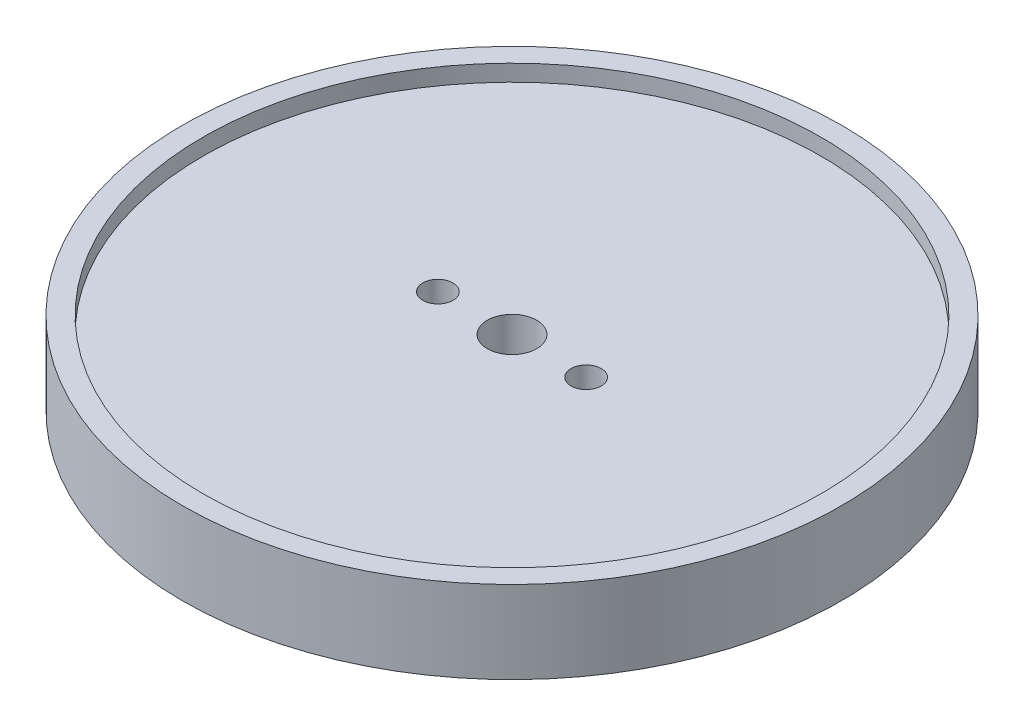
SolidWorks part; units mm, degrees
ref_plane "Front Plane" through (0, 0, 0) normal (0, 0, 1) x (1, 0, 0)
ref_plane "Top Plane" through (0, 0, 0) normal (0, 1, 0) x (1, 0, 0)
ref_plane "Right Plane" through (0, 0, 0) normal (1, 0, 0) x (0, 0, -1)
sketch "Sketch2" plane through (0, 0, 0) normal (0, 1, 0) x (1, 0, 0)
  line L0 (0, 0) -> (9, 0) construction
  line L1 (0, 0) -> (0, 20.4928) construction
  circle A0 centre (0, 0) radius 40
  circle A1 centre (0, 0) radius 3
  circle A2 centre (9, 0) radius 1.835
  circle A3 centre (-9, 0) radius 1.835
  circle A4 centre (0, 0) radius 37.5
  dimension "D1" = 80
  dimension "D2" = 6
  dimension "D4" = 3.67
  dimension "D5" = 75
  dimension "D3" = 9
extrude "Boss-Extrude1" add sketch "Sketch2" along normal blind 10 contours A0 A4 region at (-38.8686, 0, 0)
extrude "Boss-Extrude2" add sketch "Sketch2<4>" along normal blind 8 contours A4 A3 A2 A1 region at (-36.4393, 0, 0)
sketch "Sketch2<4>" plane through (0, 0, 0) normal (0, 1, 0) x (1, 0, 0) same geometry as "Sketch2"
